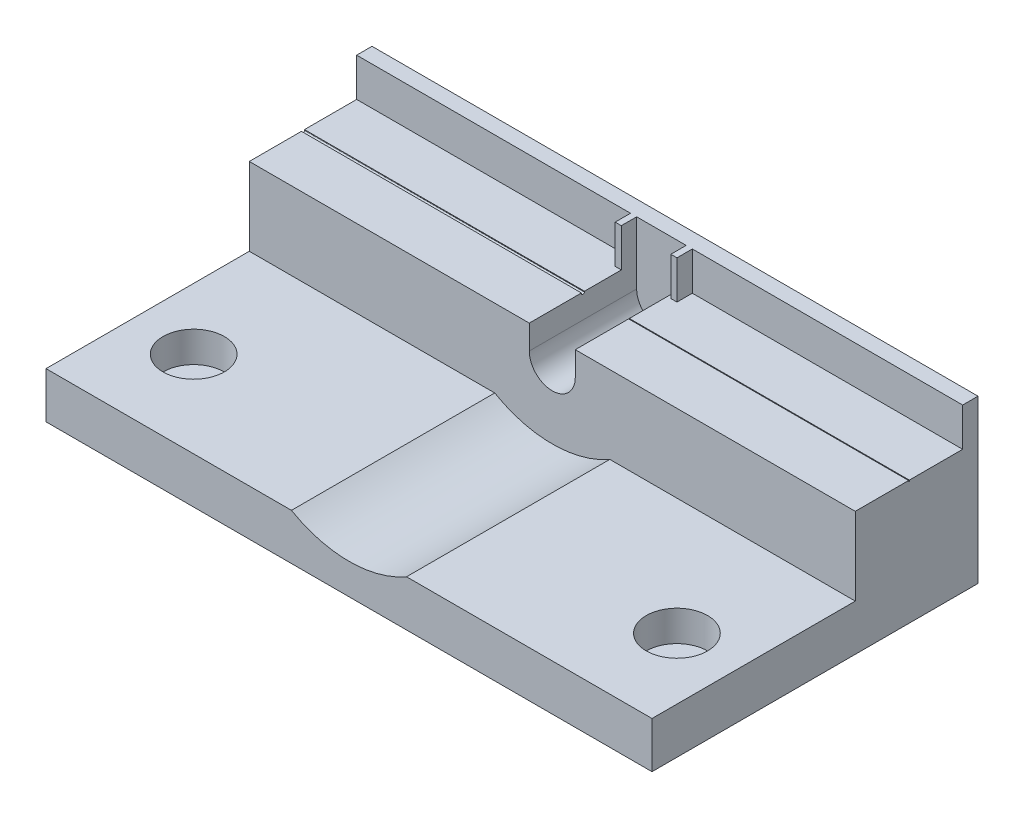
SolidWorks part; units mm, degrees
ref_plane "Front Plane" through (0, 0, 0) normal (0, 0, 1) x (1, 0, 0)
ref_plane "Top Plane" through (0, 0, 0) normal (0, 1, 0) x (1, 0, 0)
ref_plane "Right Plane" through (0, 0, 0) normal (1, 0, 0) x (0, 0, -1)
sketch "MOTOR HOLDER" plane through (0, 0, 0) normal (0, 0, 1) x (1, 0, 0)
  line L4 (-19.75, -9.5) -> (19.75, -9.5)
  line L10 (-4.3801, 0) -> (4.4896, 0) construction
  line L11 (4.4896, -0.425) -> (4.4896, -1.425) construction
  line L13 (-3.75, -6.4952) -> (0, 0) construction
  line L14 (0, 0) -> (3.75, -6.4952) construction
  line L15 (-3.75, -6.4952) -> (-19.75, -6.4952)
  line L16 (-19.75, -6.4952) -> (-19.75, -9.5)
  line L17 (3.75, -6.4952) -> (19.75, -6.4952)
  line L18 (19.75, -6.4952) -> (19.75, -9.5)
  arc A1 (-3.75, -6.4952) -> (3.75, -6.4952) centre (0, 0) ccw
  point P3 (0, -7.5)
  point P6 (0, -7.5)
  dimension "D1" = 16
  dimension "D2" = 60
  dimension "D3" = 16
  dimension "D4" = 2
extrude "Motor Holder Body Extrude" add sketch "MOTOR HOLDER" against normal blind 13.25
sketch "ROLLER HOLDER" plane through (0, 0, -13.25) normal (0, 0, -1) x (-1, 0, 0)
  line L5 (19.75, -9.5) -> (-19.75, -9.5)
  line L6 (19.75, -9.5) -> (-19.75, -9.5) construction
  line L9 (-1.0291, -1.5) -> (0.9717, -1.5) construction
  line L15 (-1.5, -3) -> (-1.5, -1.425)
  line L19 (1.5, -3) -> (1.5, -1.425)
  line L28 (1.5, -1.425) -> (19.75, -1.425)
  line L29 (19.75, -1.425) -> (19.75, -9.5)
  line L30 (-1.5, -1.425) -> (-19.75, -1.425)
  line L31 (-19.75, -1.425) -> (-19.75, -9.5)
  circle A5 centre (0, 0) radius 1.5 construction
  circle A6 centre (0, -3) radius 1.5 construction
  arc A7 (-1.5, -3) -> (1.5, -3) centre (0, -3) ccw
  point P15 (0, -1.5)
  point P20 (0, 0)
  point P23 (0, -1.5)
  dimension "D1" = 0.075
  dimension "D2" = 0.075
  dimension "D3" = 18.25
  dimension "D4" = 18.25
extrude "Roller Holder Body Extrude" add sketch "ROLLER HOLDER" along normal blind 7
sketch "ALIGNER" plane through (0, 0, -20.25) normal (0, 0, -1) x (-1, 0, 0)
  line L1 (-19.75, 1.075) -> (-19.75, -9.5)
  line L2 (-19.75, -9.5) -> (19.75, -9.5) construction
  line L4 (-19.75, -9.5) -> (19.75, -9.5)
  line L5 (19.75, -9.5) -> (19.75, 1.075)
  line L6 (-19.75, 1.075) -> (19.75, 1.075)
  line L8 (-0.1146, 1.075) -> (-0.1146, -1.425) construction
  line L11 (-2.1292, -1.425) -> (-2.1292, 1.075)
  line L13 (-1.7292, -1.425) -> (-2.1292, -1.425)
  line L14 (-0.1146, 1.075) -> (-0.4, 1.075)
  line L16 (-1.7292, -1.425) -> (-1.7292, 1.075)
  line L17 (1.5, -1.425) -> (1.9, -1.425)
  line L18 (1.5, -1.425) -> (1.5, 1.075)
  line L19 (1.5, 1.075) -> (1.9, 1.075)
  line L20 (1.9, -1.425) -> (1.9, 1.075)
  line L21 (-2.1292, 1.075) -> (-1.7292, 1.075)
  line L22 (-19.75, -1.425) -> (-19.75, -9.5) construction
  point P2 (0, 0.75)
  point P7 (19.75, -9.5)
  line M18 (-19.75, -9.5) -> (19.75, -9.5)
  line M34 (19.75, -1.425) -> (1.5, -1.425)
  dimension "D1" = 1.5
  dimension "D3" = 0.4
  dimension "D4" = 2.5
extrude "Alignment Rail Extrude" add sketch "ALIGNER<4>" against normal blind 1 contours L20 L6 L18 M34 | L11 L21 L16 L13 region at (-1.7, -0.175, -20.25)
sketch "ALIGNER<4>" plane through (0, 0, -20.25) normal (0, 0, -1) x (-1, 0, 0) same geometry as "ALIGNER"
extrude "Alignment Wall Extrude" add sketch "ALIGNER" along normal blind 1 contours L6 L1 | M18 | L6 | L18 L6 | L20 L5 L6 | L6 L5 L4 L1 region at (-0.0006, -4.2319, -20.25) region at (1.9292, -0.175, -20.25)
sketch "ELECTRODE GROOVE" plane through (19.75, 0, 0) normal (1, 0, 0) x (0, 0, -1)
  line L1 (16.725, -1.425) -> (16.775, -1.425)
  line L5 (16.725, -1.425) -> (16.725, -1.475)
  line L6 (16.775, -1.475) -> (16.775, -1.425)
  line L7 (20.25, -1.425) -> (13.25, -1.425) construction
  arc A0 (16.725, -1.475) -> (16.775, -1.475) centre (16.75, -1.475) ccw
  point P5 (16.75, -1.425)
  point P6 (16.75, -1.425)
  point P8 (16.75, -1.475)
  point P9 (16.75, -1.425)
  dimension "D1" = 0.05
extrude "Electrode Groove Cut Extrude" cut sketch "ELECTRODE GROOVE" against normal up to surface (18.25 mm away) up to face at (1.5, -2.2125, -16.75)
sketch "FIBRE GROOVE" plane through (-19.75, 0, 0) normal (-1, 0, 0) x (0, 0, 1)
  line L0 (-20.25, -1.425) -> (-13.25, -1.425) construction
  line L1 (-16.85, -1.425) -> (-16.85, -1.475)
  line L2 (-16.85, -1.425) -> (-16.65, -1.425)
  line L6 (-16.65, -1.425) -> (-16.65, -1.475)
  arc A0 (-16.85, -1.475) -> (-16.65, -1.475) centre (-16.75, -1.455) ccw
  point P0 (-16.75, -1.425)
  point P2 (-16.75, -1.425)
  point P3 (0, 0)
  point P5 (-16.75, -1.425)
  point P9 (-20, -0.705)
  point P12 (0, 0)
  dimension "D2" = 0.05
  dimension "D1" = 0.2
  dimension "D3" = 0.05
  dimension "D4" = 0.03
extrude "Fibre Groove Cut Extrude" cut sketch "FIBRE GROOVE" against normal up to surface (18.25 mm away) up to face at (-1.5, -1.1167, -17.5833)
sketch "REFERENCE" plane through (0, -9.5, 0) normal (0, -1, 0) x (-1, 0, 0)
  point P0 (0, 13)
sketch "ADJUSTMENT SCREW HOLES" plane through (0, -6.4952, 0) normal (0, 1, 0) x (1, 0, 0)
  line L2 (19.75, 13.25) -> (19.75, 0) construction
  line L3 (-19.75, 13.25) -> (-19.75, 0) construction
  line L4 (-19.75, 11.25) -> (19.75, 11.25) construction
  line L6 (-19.75, 11.25) -> (-19.75, 0) construction
  line L7 (19.75, 11.25) -> (19.75, 0) construction
  line L8 (-19.75, 13.25) -> (-1.5, 13.25) construction
  circle A2 centre (-15.75, 5.625) radius 2
  circle A4 centre (15.75, 5.625) radius 2
  point P14 (-19.75, 5.625)
  point P19 (19.75, 5.625)
  dimension "D1" = 4
  dimension "D2" = 4
  dimension "D3" = 2
extrude "Adjustment Screw Holes Cut Extrude" cut sketch "ADJUSTMENT SCREW HOLES" against normal blind 2
